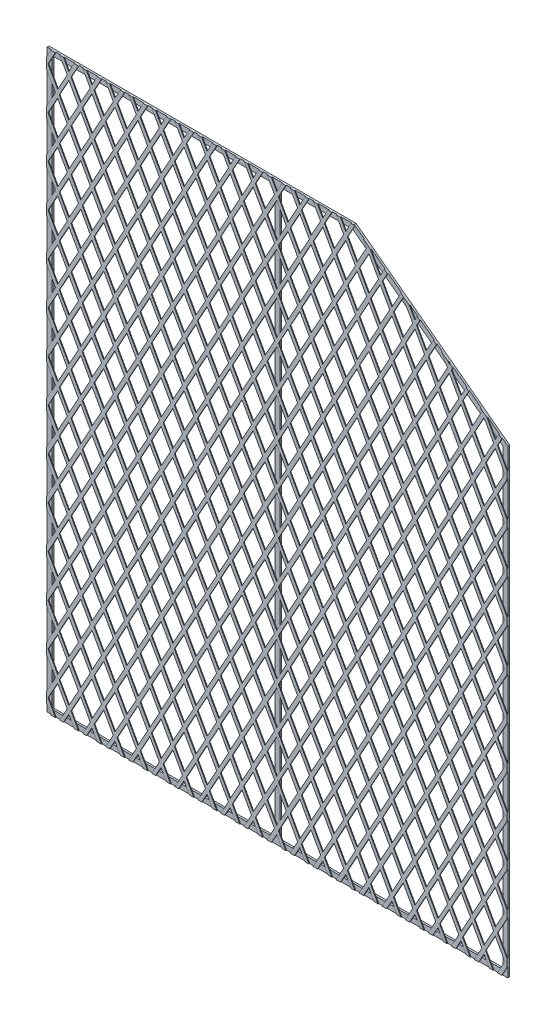
SolidWorks part; units mm, degrees
material "Acero al carbono fundido"
ref_plane "Alzado" through (0, 0, 0) normal (0, 0, 1) x (1, 0, 0)
ref_plane "Planta" through (0, 0, 0) normal (0, 1, 0) x (1, 0, 0)
ref_plane "Vista lateral" through (0, 0, 0) normal (1, 0, 0) x (0, 0, -1)
sketch "Croquis1" plane through (0, 0, 0) normal (0, 0, 1) x (1, 0, 0)
  line L17 (0, 0) -> (0, 1500)
  line L18 (0, 1500) -> (800, 1500)
  line L19 (800, 1500) -> (1200, 1200)
  line L20 (1200, 1200) -> (1200, 0)
  line L21 (1200, 0) -> (0, 0)
  line L22 (12.7, 12.7) -> (12.7, 1487.3)
  line L23 (12.7, 1487.3) -> (593.65, 1487.3)
  line L24 (795.7667, 1487.3) -> (1187.3, 1193.65)
  line L25 (1187.3, 1193.65) -> (1187.3, 12.7)
  line L26 (1187.3, 12.7) -> (606.35, 12.7)
  line L27 (593.65, 12.7) -> (593.65, 1487.3)
  line L28 (606.35, 1487.3) -> (606.35, 12.7)
  line L29 (593.65, 12.7) -> (12.7, 12.7)
  line L30 (1187.3, 12.7) -> (12.7, 12.7) construction
  line L31 (606.35, 1487.3) -> (795.7667, 1487.3)
  line L32 (12.7, 1487.3) -> (795.7667, 1487.3) construction
  point P15 (600, 0)
  dimension "D1" = 1500
  dimension "D2" = 1200
  dimension "D3" = 800
  dimension "D4" = 1200
  dimension "D6" = 12.7
  dimension "D7" = 6.35
  dimension "D5" = 12.7
extrude "Saliente-Extruir1" add sketch "Croquis1" along normal blind 4.8
sketch "Croquis2" plane through (0, 0, 4.8) normal (0, 0, 1) x (1, 0, 0)
  line L0 (0, 1500) -> (800, 1500)
  line L1 (800, 1500) -> (1200, 1200)
  line L2 (1200, 1200) -> (1200, 0)
  line L3 (1200, 0) -> (0, 0)
  line L4 (0, 0) -> (0, 1500)
extrude "Saliente-Extruir2" add sketch "Croquis2" along normal blind 1.9
sketch "Croquis3" plane through (0, 0, 6.7) normal (0, 0, 1) x (1, 0, 0)
  line L0 (600, 0) -> (600, 1500) construction
  line L1 (0, 0) -> (1200, 0) construction
  line L2 (800, 1500) -> (0, 1500) construction
  line L3 (0, 750) -> (1200, 750) construction
  line L4 (0, 1500) -> (0, 0) construction
  line L5 (1200, 0) -> (1200, 1200) construction
  line L6 (600, 795) -> (625, 750)
  line L7 (625, 750) -> (600, 705)
  line L8 (600, 705) -> (575, 750)
  line L9 (575, 750) -> (600, 795)
  line L10 (538.5604, 795) -> (563.5604, 750)
  line L11 (563.5604, 750) -> (538.5604, 705)
  line L12 (538.5604, 705) -> (513.5604, 750)
  line L13 (513.5604, 750) -> (538.5604, 795)
  line L14 (569.2802, 850.2956) -> (594.2802, 805.2956)
  line L15 (594.2802, 805.2956) -> (569.2802, 760.2956)
  line L16 (569.2802, 760.2956) -> (544.2802, 805.2956)
  line L17 (544.2802, 805.2956) -> (569.2802, 850.2956)
  line L18 (503.5604, 750) -> (478.5604, 705)
  line L19 (478.5604, 705) -> (453.5604, 750)
  line L20 (453.5604, 750) -> (478.5604, 795)
  line L21 (478.5604, 795) -> (503.5604, 750)
  line L22 (484.2802, 805.2956) -> (509.2802, 850.2956)
  line L23 (509.2802, 760.2956) -> (484.2802, 805.2956)
  line L24 (534.2802, 805.2956) -> (509.2802, 760.2956)
  line L25 (509.2802, 850.2956) -> (534.2802, 805.2956)
  line L26 (443.5604, 750) -> (418.5604, 705)
  line L27 (418.5604, 705) -> (393.5604, 750)
  line L28 (393.5604, 750) -> (418.5604, 795)
  line L29 (418.5604, 795) -> (443.5604, 750)
  line L30 (424.2802, 805.2956) -> (449.2802, 850.2956)
  line L31 (449.2802, 760.2956) -> (424.2802, 805.2956)
  line L32 (474.2802, 805.2956) -> (449.2802, 760.2956)
  line L33 (449.2802, 850.2956) -> (474.2802, 805.2956)
  line L34 (383.5604, 750) -> (358.5604, 705)
  line L35 (358.5604, 705) -> (333.5604, 750)
  line L36 (333.5604, 750) -> (358.5604, 795)
  line L37 (358.5604, 795) -> (383.5604, 750)
  line L38 (364.2802, 805.2956) -> (389.2802, 850.2956)
  line L39 (389.2802, 760.2956) -> (364.2802, 805.2956)
  line L40 (414.2802, 805.2956) -> (389.2802, 760.2956)
  line L41 (389.2802, 850.2956) -> (414.2802, 805.2956)
  line L42 (323.5604, 750) -> (298.5604, 705)
  line L43 (298.5604, 705) -> (273.5604, 750)
  line L44 (273.5604, 750) -> (298.5604, 795)
  line L45 (298.5604, 795) -> (323.5604, 750)
  line L46 (304.2802, 805.2956) -> (329.2802, 850.2956)
  line L47 (329.2802, 760.2956) -> (304.2802, 805.2956)
  line L48 (354.2802, 805.2956) -> (329.2802, 760.2956)
  line L49 (329.2802, 850.2956) -> (354.2802, 805.2956)
  line L50 (263.5604, 750) -> (238.5604, 705)
  line L51 (238.5604, 705) -> (213.5604, 750)
  line L52 (213.5604, 750) -> (238.5604, 795)
  line L53 (238.5604, 795) -> (263.5604, 750)
  line L54 (244.2802, 805.2956) -> (269.2802, 850.2956)
  line L55 (269.2802, 760.2956) -> (244.2802, 805.2956)
  line L56 (294.2802, 805.2956) -> (269.2802, 760.2956)
  line L57 (269.2802, 850.2956) -> (294.2802, 805.2956)
  line L58 (203.5604, 750) -> (178.5604, 705)
  line L59 (178.5604, 705) -> (153.5604, 750)
  line L60 (153.5604, 750) -> (178.5604, 795)
  line L61 (178.5604, 795) -> (203.5604, 750)
  line L62 (184.2802, 805.2956) -> (209.2802, 850.2956)
  line L63 (209.2802, 760.2956) -> (184.2802, 805.2956)
  line L64 (234.2802, 805.2956) -> (209.2802, 760.2956)
  line L65 (209.2802, 850.2956) -> (234.2802, 805.2956)
  line L66 (143.5604, 750) -> (118.5604, 705)
  line L67 (118.5604, 705) -> (93.5604, 750)
  line L68 (93.5604, 750) -> (118.5604, 795)
  line L69 (118.5604, 795) -> (143.5604, 750)
  line L70 (124.2802, 805.2956) -> (149.2802, 850.2956)
  line L71 (149.2802, 760.2956) -> (124.2802, 805.2956)
  line L72 (174.2802, 805.2956) -> (149.2802, 760.2956)
  line L73 (149.2802, 850.2956) -> (174.2802, 805.2956)
  line L74 (83.5604, 750) -> (58.5604, 705)
  line L75 (58.5604, 705) -> (33.5604, 750)
  line L76 (33.5604, 750) -> (58.5604, 795)
  line L77 (58.5604, 795) -> (83.5604, 750)
  line L78 (64.2802, 805.2956) -> (89.2802, 850.2956)
  line L79 (89.2802, 760.2956) -> (64.2802, 805.2956)
  line L80 (114.2802, 805.2956) -> (89.2802, 760.2956)
  line L81 (89.2802, 850.2956) -> (114.2802, 805.2956)
  line L82 (23.5604, 750) -> (-1.4396, 705)
  line L83 (-1.4396, 705) -> (-26.4396, 750)
  line L84 (-26.4396, 750) -> (-1.4396, 795)
  line L85 (-1.4396, 795) -> (23.5604, 750)
  line L86 (4.2802, 805.2956) -> (29.2802, 850.2956)
  line L87 (29.2802, 760.2956) -> (4.2802, 805.2956)
  line L88 (54.2802, 805.2956) -> (29.2802, 760.2956)
  line L89 (29.2802, 850.2956) -> (54.2802, 805.2956)
  line L90 (629.2802, 760.2956) -> (604.2802, 805.2956)
  line L91 (604.2802, 805.2956) -> (629.2802, 850.2956)
  line L92 (629.2802, 850.2956) -> (654.2802, 805.2956)
  line L93 (654.2802, 805.2956) -> (629.2802, 760.2956)
  line L94 (660, 705) -> (635, 750)
  line L95 (660, 795) -> (685, 750)
  line L96 (685, 750) -> (660, 705)
  line L97 (635, 750) -> (660, 795)
  line L98 (689.2802, 760.2956) -> (664.2802, 805.2956)
  line L99 (664.2802, 805.2956) -> (689.2802, 850.2956)
  line L100 (689.2802, 850.2956) -> (714.2802, 805.2956)
  line L101 (714.2802, 805.2956) -> (689.2802, 760.2956)
  line L102 (720, 705) -> (695, 750)
  line L103 (720, 795) -> (745, 750)
  line L104 (745, 750) -> (720, 705)
  line L105 (695, 750) -> (720, 795)
  line L106 (749.2802, 760.2956) -> (724.2802, 805.2956)
  line L107 (724.2802, 805.2956) -> (749.2802, 850.2956)
  line L108 (749.2802, 850.2956) -> (774.2802, 805.2956)
  line L109 (774.2802, 805.2956) -> (749.2802, 760.2956)
  line L110 (780, 705) -> (755, 750)
  line L111 (780, 795) -> (805, 750)
  line L112 (805, 750) -> (780, 705)
  line L113 (755, 750) -> (780, 795)
  line L114 (809.2802, 760.2956) -> (784.2802, 805.2956)
  line L115 (784.2802, 805.2956) -> (809.2802, 850.2956)
  line L116 (809.2802, 850.2956) -> (834.2802, 805.2956)
  line L117 (834.2802, 805.2956) -> (809.2802, 760.2956)
  line L118 (840, 705) -> (815, 750)
  line L119 (840, 795) -> (865, 750)
  line L120 (865, 750) -> (840, 705)
  line L121 (815, 750) -> (840, 795)
  line L122 (869.2802, 760.2956) -> (844.2802, 805.2956)
  line L123 (844.2802, 805.2956) -> (869.2802, 850.2956)
  line L124 (869.2802, 850.2956) -> (894.2802, 805.2956)
  line L125 (894.2802, 805.2956) -> (869.2802, 760.2956)
  line L126 (900, 705) -> (875, 750)
  line L127 (900, 795) -> (925, 750)
  line L128 (925, 750) -> (900, 705)
  line L129 (875, 750) -> (900, 795)
  line L130 (929.2802, 760.2956) -> (904.2802, 805.2956)
  line L131 (904.2802, 805.2956) -> (929.2802, 850.2956)
  line L132 (929.2802, 850.2956) -> (954.2802, 805.2956)
  line L133 (954.2802, 805.2956) -> (929.2802, 760.2956)
  line L134 (960, 705) -> (935, 750)
  line L135 (960, 795) -> (985, 750)
  line L136 (985, 750) -> (960, 705)
  line L137 (935, 750) -> (960, 795)
  line L138 (989.2802, 760.2956) -> (964.2802, 805.2956)
  line L139 (964.2802, 805.2956) -> (989.2802, 850.2956)
  line L140 (989.2802, 850.2956) -> (1014.2802, 805.2956)
  line L141 (1014.2802, 805.2956) -> (989.2802, 760.2956)
  line L142 (1020, 705) -> (995, 750)
  line L143 (1020, 795) -> (1045, 750)
  line L144 (1045, 750) -> (1020, 705)
  line L145 (995, 750) -> (1020, 795)
  line L146 (1049.2802, 760.2956) -> (1024.2802, 805.2956)
  line L147 (1024.2802, 805.2956) -> (1049.2802, 850.2956)
  line L148 (1049.2802, 850.2956) -> (1074.2802, 805.2956)
  line L149 (1074.2802, 805.2956) -> (1049.2802, 760.2956)
  line L150 (1080, 705) -> (1055, 750)
  line L151 (1080, 795) -> (1105, 750)
  line L152 (1105, 750) -> (1080, 705)
  line L153 (1055, 750) -> (1080, 795)
  line L154 (1109.2802, 760.2956) -> (1084.2802, 805.2956)
  line L155 (1084.2802, 805.2956) -> (1109.2802, 850.2956)
  line L156 (1109.2802, 850.2956) -> (1134.2802, 805.2956)
  line L157 (1134.2802, 805.2956) -> (1109.2802, 760.2956)
  line L158 (1140, 705) -> (1115, 750)
  line L159 (1140, 795) -> (1165, 750)
  line L160 (1165, 750) -> (1140, 705)
  line L161 (1115, 750) -> (1140, 795)
  line L162 (1169.2802, 760.2956) -> (1144.2802, 805.2956)
  line L163 (1144.2802, 805.2956) -> (1169.2802, 850.2956)
  line L164 (1169.2802, 850.2956) -> (1194.2802, 805.2956)
  line L165 (1194.2802, 805.2956) -> (1169.2802, 760.2956)
  line L166 (1200, 705) -> (1175, 750)
  line L167 (1200, 795) -> (1225, 750)
  line L168 (1225, 750) -> (1200, 705)
  line L169 (1175, 750) -> (1200, 795)
  dimension "D1" = 90
  dimension "D2" = 50
  dimension "D4" = 10
  dimension "D5" = 50
  dimension "D6" = 10
  dimension "D7" = 10
  dimension "D3" = 2
  dimension "D8" = 11
extrude "Cortar-Extruir1" cut sketch "Croquis3" against normal blind 1.9
pattern_linear "MatrizL1" count 8 spacing 110 along (0, -1, 0) of "Cortar-Extruir1"
pattern_linear "MatrizL2" count 8 spacing 110 along (0, 1, 0) of "Cortar-Extruir1"
